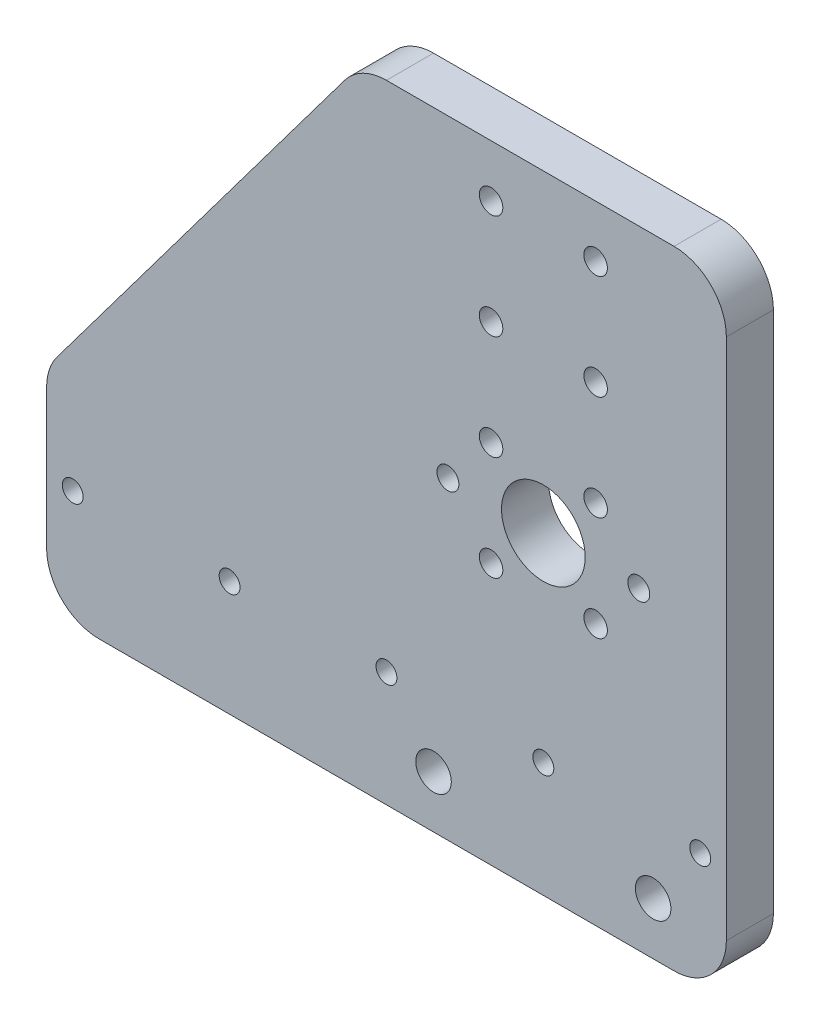
SolidWorks part; units mm, degrees
ref_plane "Front" through (0, 0, 0) normal (0, 0, 1) x (1, 0, 0)
ref_plane "Top" through (0, 0, 0) normal (0, 1, 0) x (1, 0, 0)
ref_plane "Right" through (0, 0, 0) normal (1, 0, 0) x (0, 0, -1)
sketch "Esquisse1" plane through (0, 0, 0) normal (0, 0, 1) x (1, 0, 0)
  line L0 (0, 0) -> (130, 0)
  line L1 (130, 0) -> (130, 120)
  line L2 (130, 120) -> (60, 120)
  line L3 (60, 120) -> (0, 40)
  line L4 (0, 40) -> (0, 0)
  dimension "D1" = 120
  dimension "D2" = 130
  dimension "D3" = 40
  dimension "D4" = 70
extrude "Boss.-Extru.1" add sketch "Esquisse1" along normal blind 9
sketch "Esquisse2" plane through (0, 0, 9) normal (0, 0, 1) x (1, 0, 0)
  line L0 (0, 22) -> (130, 22) construction
  line L1 (0, 40) -> (0, 0) construction
  line L2 (130, 0) -> (130, 120) construction
  line L3 (65, 22) -> (65, 26.8679) construction
  line L4 (0, 0) -> (130, 0) construction
  line L5 (95, 120) -> (95, 80) construction
  line L6 (130, 120) -> (60, 120) construction
  line L7 (95, 100) -> (92.3142, 100) construction
  line L8 (95, 80) -> (85.6936, 80) construction
  line L9 (95, 60) -> (92.3142, 60) construction
  circle A0 centre (65, 22) radius 2
  circle A1 centre (35, 22) radius 2
  circle A2 centre (5, 22) radius 2
  circle A3 centre (125, 22) radius 2
  circle A4 centre (95, 22) radius 2
  circle A5 centre (85, 110) radius 2.25
  circle A6 centre (85, 90) radius 2.25
  circle A7 centre (105, 90) radius 2.25
  circle A8 centre (105, 110) radius 2.25
  circle A9 centre (105, 50) radius 2.25
  circle A10 centre (105, 70) radius 2.25
  circle A11 centre (85, 70) radius 2.25
  circle A12 centre (85, 50) radius 2.25
  dimension "D1" = 4
  dimension "D2" = 30
  dimension "D3" = 30
  dimension "D6" = 20
  dimension "D7" = 10
  dimension "D8" = 4.5
  dimension "D4" = 22
  dimension "D5" = 20
extrude "Enlèv. mat.-Extru.1" cut sketch "Esquisse2" against normal through all
sketch "Esquisse3" plane through (0, 0, 9) normal (0, 0, 1) x (1, 0, 0)
  line L0 (85, 50) -> (105, 70) construction
  line L1 (95, 60) -> (95, 10) construction
  line L2 (95, 10) -> (74, 10) construction
  circle A0 centre (95, 60) radius 8
  circle A1 centre (74, 10) radius 3.4
  circle A2 centre (116, 10) radius 3.4
  dimension "D1" = 16
  dimension "D2" = 21
  dimension "D3" = 6.8
  dimension "D4" = 50
extrude "Enlèv. mat.-Extru.2" cut sketch "Esquisse3" against normal through all
fillet "Congé1" radius 10 5 edges at (0, 40, 4.5) (60, 120, 4.5) (130, 120, 4.5) (130, 0, 4.5) (0, 0, 4.5)
sketch "Esquisse5" [suppressed] plane through (0, 0, 0) normal (0, 0, -1) x (-1, 0, 0)
  line L0 (-95, 60) -> (-95, 81.9203) construction
  line L1 (-95, 60) -> (-116.9203, 60) construction
  line L2 (-95, 60) -> (-91.0893, 63.9107) construction
  line L3 (-95, 60) -> (-95, 38.0797) construction
  line L4 (-95, 60) -> (-73.0797, 60) construction
  circle A0 centre (-125, 85) radius 2
  circle A1 centre (-65, 85) radius 2
  circle A2 centre (-65, 35) radius 2
  circle A3 centre (-125, 35) radius 2
  dimension "D1" = 60
  dimension "D2" = 50
  dimension "D4" = 4
  dimension "D3" = 45
extrude "Enlèv. mat.-Extru.3" [suppressed] cut sketch "Esquisse5" against normal through all
sketch "Esquisse6" plane through (0, 0, 0) normal (0, 0, -1) x (-1, 0, 0)
  line L0 (-113.25, 60) -> (-95, 60) construction
  line L1 (-95, 60) -> (-95, 52) construction
  circle A0 centre (-113.25, 60) radius 2.1
  circle A2 centre (-95, 60) radius 8 construction
  circle A3 centre (-76.75, 60) radius 2.1
  dimension "D2" = 4.2
  dimension "D1" = 18.25
extrude "Enlèv. mat.-Extru.4" cut sketch "Esquisse6" against normal through all
